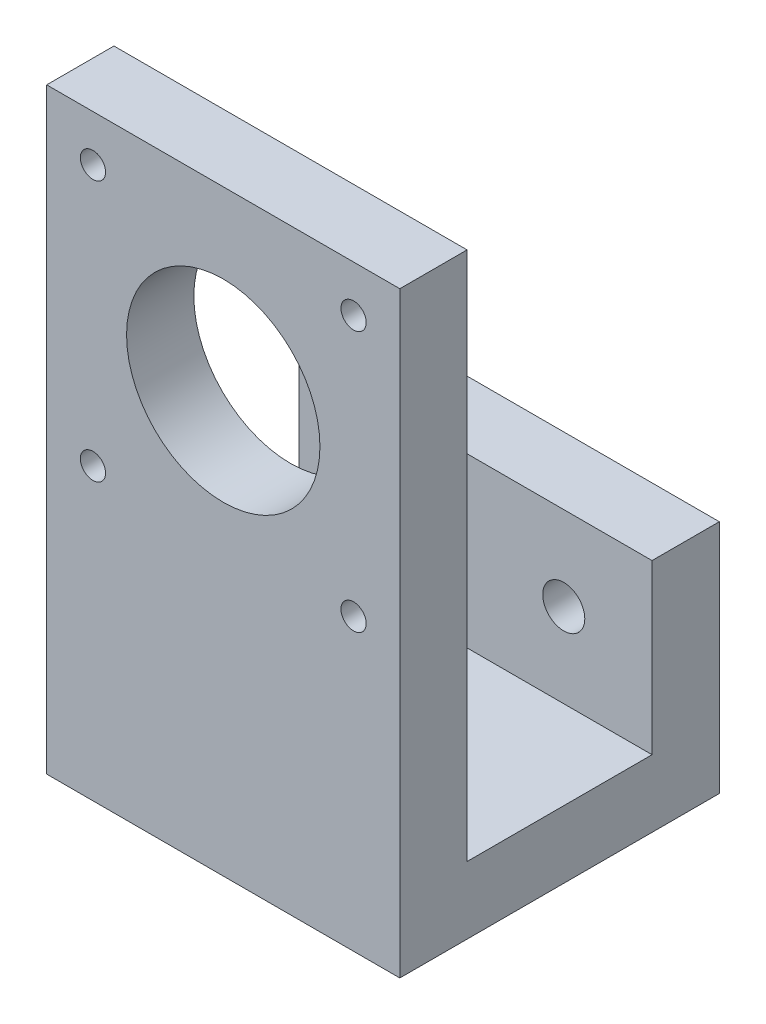
SolidWorks part; units mm, degrees
ref_plane "前视基准面" through (0, 0, 0) normal (0, 0, 1) x (1, 0, 0)
ref_plane "上视基准面" through (0, 0, 0) normal (0, 1, 0) x (1, 0, 0)
ref_plane "右视基准面" through (0, 0, 0) normal (1, 0, 0) x (0, 0, -1)
sketch "草图1" plane through (0, 0, 0) normal (0, 0, 1) x (1, 0, 0)
  line L0 (-12.24, -1.4) -> (29.76, -1.4)
  line L5 (-12.24, 18.6) -> (29.76, 18.6)
  line L6 (-12.24, 18.6) -> (-12.24, -9.4)
  line L7 (-12.24, -9.4) -> (29.76, -9.4)
  line L8 (29.76, 18.6) -> (29.76, -9.4)
  line L9 (-12.24, 18.6) -> (29.76, -1.4) construction
  line L10 (29.76, -1.4) -> (29.76, 18.6) construction
  line L11 (-12.24, -1.4) -> (29.76, 18.6) construction
  line L12 (8.76, 18.6) -> (8.76, -1.4) construction
  line L13 (8.76, -1.4) -> (-12.24, 18.6) construction
  line L14 (8.76, 18.6) -> (29.76, -1.4) construction
  circle A0 centre (-1.74, 8.6) radius 2.5
  circle A1 centre (19.26, 8.6) radius 2.5
  point P4 (-12.24, -1.4)
  dimension "D1" = 42
  dimension "D2" = 28
  dimension "D3" = 8
extrude "凸台-拉伸1" add sketch "草图1" along normal blind 8 contours L8 L5 L6 L0 A1 A0 region at (8.76, 8.6, 0)
extrude "凸台-拉伸2" add sketch "草图1<3>" along normal blind 30 contours L8 L0 L6 L7 region at (8.76, -5.4, 0)
sketch "草图1<3>" plane through (0, 0, 0) normal (0, 0, 1) x (1, 0, 0) same geometry as "草图1"
sketch "草图2" plane through (0, 0, 30) normal (0, 0, 1) x (1, 0, 0)
  line L0 (-12.24, 19.6) -> (29.76, 19.6) construction
  line L1 (29.76, -9.4) -> (-12.24, -9.4)
  line L2 (29.76, -9.4) -> (29.76, 61.6)
  line L3 (29.76, 61.6) -> (-12.24, 61.6)
  line L4 (-12.24, -9.4) -> (-12.24, 61.6)
  line L5 (29.76, 19.6) -> (-12.24, 61.6) construction
  line L6 (29.76, 61.6) -> (-12.24, 19.6) construction
  line L12 (-6.74, 56.1) -> (24.26, 25.1) construction
  line L13 (-6.74, 25.1) -> (24.26, 56.1) construction
  circle A0 centre (24.26, 56.1) radius 1.5
  circle A1 centre (-6.74, 56.1) radius 1.5
  circle A2 centre (-6.74, 25.1) radius 1.5
  circle A3 centre (24.26, 25.1) radius 1.5
  circle A4 centre (8.76, 40.6) radius 11.5
  point P5 (-12.24, 19.6)
  point P8 (8.76, 40.6)
  dimension "D1" = 42
  dimension "D2" = 71
  dimension "D3" = 42
  dimension "D4" = 31
  dimension "D5" = 31
extrude "凸台-拉伸3" add sketch "草图2" along normal blind 8
